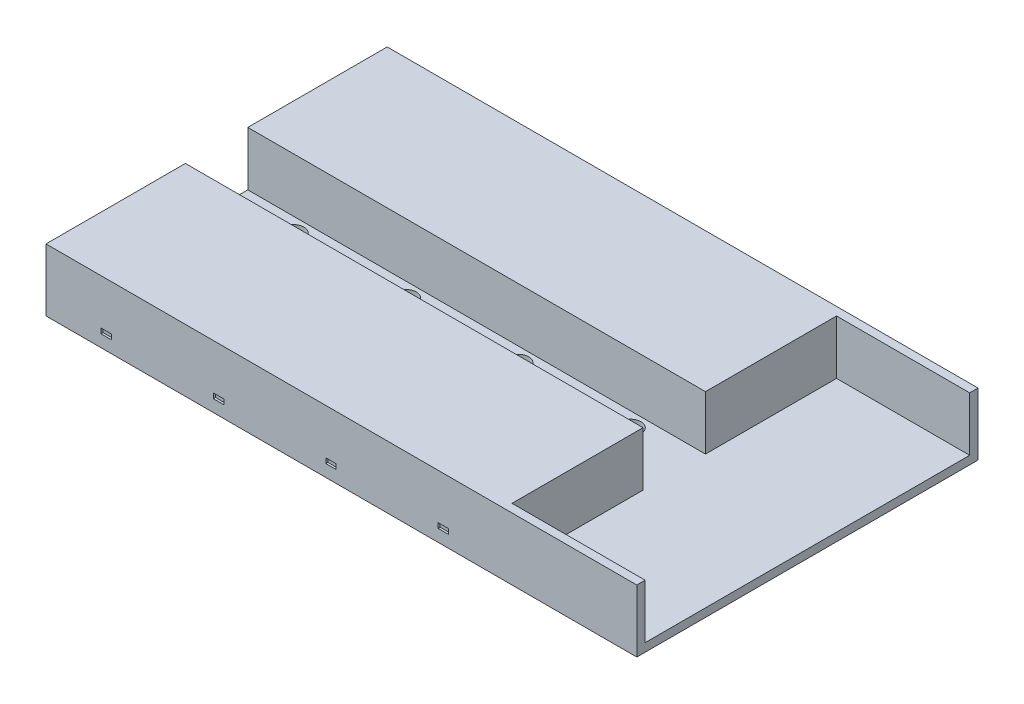
SolidWorks part; units mm, degrees
ref_plane "前视基准面" through (0, 0, 0) normal (0, 0, 1) x (1, 0, 0)
ref_plane "上视基准面" through (0, 0, 0) normal (0, 1, 0) x (1, 0, 0)
ref_plane "右视基准面" through (0, 0, 0) normal (1, 0, 0) x (0, 0, -1)
sketch "草图3" plane through (0, 0, 0) normal (0, 1, 0) x (1, 0, 0)
  line L0 (0, 0) -> (-71, 0)
  line L1 (-71, 0) -> (-71, 41)
  line L2 (-71, 41) -> (71, 41)
  line L3 (71, 41) -> (71, 0)
  line L4 (0, 0) -> (71, 0)
extrude "凸台-拉伸1" add sketch "草图3" along normal blind 15
sketch "草图4" plane through (0, 0, 0) normal (0, 1, 0) x (1, 0, 0)
  line L0 (-69, 39) -> (-69, 9.5)
  line L1 (-69, 9.5) -> (-44, 9.5)
  line L3 (-69, 39) -> (-44, 39)
  line L4 (-44, 9.5) -> (-44, 39)
  dimension "D1" = 29.5
extrude "切除-拉伸2" cut sketch "草图4" along normal offset from surface (13 mm away) 2 up to face at (0, 15, -20.5)
ref_axis "基准轴1" through (-71, 15, 0) along (1, 0, 0)
pattern_linear "阵列(线性)1" count 4 spacing 27 along (1, 0, 0) of "切除-拉伸2"
sketch "草图6" plane through (71, 0, 0) normal (1, 0, 0) x (0, 0, -1)
  line L0 (0, 15) -> (7.5, 15)
  line L1 (0, 15) -> (41, 15) construction
  line L2 (7.5, 15) -> (7.5, 2)
  line L3 (7.5, 2) -> (0, 2)
  line L4 (0, 15) -> (0, 0) construction
  line L5 (0, 2) -> (0, 15)
extrude "切除-拉伸3" cut sketch "草图6" against normal through all
sketch "草图7" plane through (71, 0, 0) normal (1, 0, 0) x (0, 0, -1)
  line L0 (0, 0) -> (4, 0)
  line L1 (0, 0) -> (0, -4)
  arc A0 (0, -4) -> (4, 0) centre (0, 0) ccw
extrude "凸台-拉伸2" add sketch "草图7" against normal up to surface (142 mm away) up to face at (-71, 5.6667, -16.1667)
sketch "草图8" plane through (71, 0, 0) normal (1, 0, 0) x (0, 0, -1)
  line L0 (0, -1) -> (0, -2)
  line L4 (0, 2) -> (0, -4) construction
  line L5 (0, -2) -> (0, -3)
  arc A0 (0, -3) -> (0, -1) centre (0, -2) ccw
extrude "切除-拉伸4" cut sketch "草图8" against normal through all
sketch "草图14" plane through (0, 0, 0) normal (0, 0, 1) x (1, 0, 0)
  line L0 (-67, -4) -> (-46, -4)
  line L1 (-46, 0) -> (-67, 0)
  line L3 (-71, -4) -> (71, -4) construction
  line L5 (-67, -4) -> (-67, 0)
  line L9 (-46, 0) -> (-46, -4)
extrude "切除-拉伸7" cut sketch "草图14" against normal through all
pattern_linear "阵列(线性)3" count 5 spacing 27 along (1, 0, 0) of "切除-拉伸7"
sketch "草图16" plane through (0, 0, 0) normal (0, 0, 1) x (1, 0, 0)
  line L0 (71, -1) -> (71, 0)
  line L1 (71, -4) -> (71, -1)
  line L2 (71, 2) -> (71, -1) construction
  line L3 (71, 0) -> (42.1782, 0)
  line L4 (42.1782, -4) -> (71, -4)
  line L8 (42.1782, -4) -> (42.1782, 0)
extrude "切除-拉伸8" cut sketch "草图16" against normal through all
sketch "草图17" plane through (0, 0, 0) normal (0, -1, 0) x (1, 0, 0)
  circle A0 centre (-56.5, -4) radius 2.5
extrude "切除-拉伸9" cut sketch "草图17" against normal through all
pattern_linear "阵列(线性)4" count 4 spacing 27 along (1, 0, 0) of "切除-拉伸9"
ref_plane "基准面13" through (0, 0, 0) normal (0, 0, 1) x (1, 0, 0)
sketch "草图21" plane through (71, 0, 0) normal (1, 0, 0) x (0, 0, -1)
  line L0 (39, 2) -> (7.5, 2)
  line L1 (7.5, 2) -> (7.5, 15)
  line L2 (7.5, 15) -> (39, 15)
  line L4 (39, 2) -> (39, 15)
  line L5 (7.5, 15) -> (41, 15) construction
extrude "切除-拉伸11" cut sketch "草图21" against normal offset from surface (32 mm away) 2 up to face at (37, 6.5, -24.25)
sketch "草图23" plane through (0, 0, -41) normal (0, 0, -1) x (-1, 0, 0)
  line L2 (55.25, 2.9) -> (56.5, 2.9)
  line L3 (56.5, 2.9) -> (57.75, 2.9)
  line L5 (55.25, 3.5) -> (55.25, 2.9)
  line L6 (57.75, 2.9) -> (57.75, 3.5)
  line L7 (57.75, 3.5) -> (57.75, 4.1)
  line L8 (57.75, 4.1) -> (55.25, 4.1)
  line L9 (55.25, 4.1) -> (55.25, 3.5)
extrude "切除-拉伸12" cut sketch "草图23" against normal blind 0.5
pattern_linear "阵列(线性)5" count 4 spacing 27 along (1, 0, 0) of "切除-拉伸12"
mirror "镜向1" about plane through (0, 0, 0) normal (0, 0, 1) of "阵列(线性)5", "切除-拉伸12", "切除-拉伸11", "阵列(线性)4", "切除-拉伸9", "切除-拉伸8", "阵列(线性)3", "切除-拉伸7", "切除-拉伸4", "凸台-拉伸2", "切除-拉伸3", "阵列(线性)1", "切除-拉伸2", "凸台-拉伸1"
